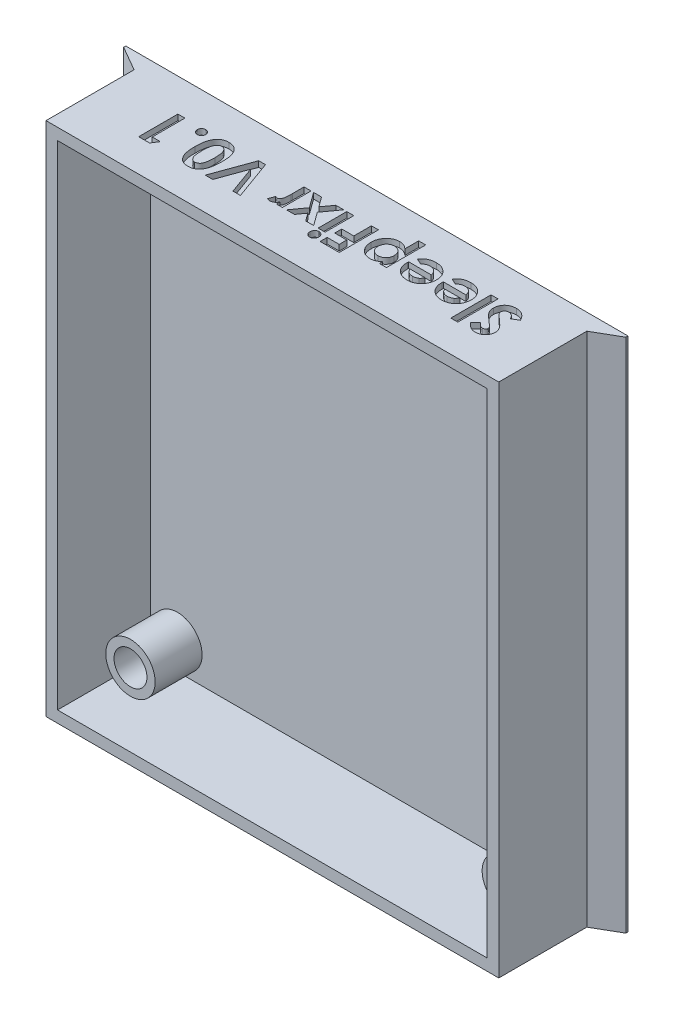
SolidWorks part; units mm, degrees
ref_plane "Front Plane" through (0, 0, 0) normal (0, 0, 1) x (1, 0, 0)
ref_plane "Top Plane" through (0, 0, 0) normal (0, 1, 0) x (1, 0, 0)
ref_plane "Right Plane" through (0, 0, 0) normal (1, 0, 0) x (0, 0, -1)
sketch "Sketch1" plane through (0, 0, 0) normal (0, 0, 1) x (1, 0, 0)
  line L0 (-27.5, 31.35) -> (27.5, -31.35) construction
  line L1 (-27.5, 31.35) -> (27.5, 31.35)
  line L2 (-27.5, 31.35) -> (-27.5, -31.35)
  line L3 (-27.5, -31.35) -> (27.5, -31.35)
  line L4 (27.5, 31.35) -> (27.5, -31.35)
  line L5 (-27.5, -31.35) -> (27.5, 31.35) construction
  point P4 (0, 0)
  dimension "D1" = 55
  dimension "D2" = 62.7
extrude "Boss-Extrude1" add sketch "Sketch1" along normal blind 12.7
shell "Shell1" thickness 1.4 removed face at (0, 0, 12.7)
sketch "Sketch2" plane through (0, 0, 1.4) normal (0, 0, 1) x (1, 0, 0)
  line L0 (24.4065, 26.6523) -> (21.3585, 26.6523) construction
  line L1 (22.8825, 28.1763) -> (22.8825, 25.1283) construction
  circle A0 centre (22.8825, 26.6523) radius 3
  circle A1 centre (22.8825, -26.6878) radius 2
  circle A2 centre (22.8825, 26.6523) radius 2
  circle A3 centre (22.8825, 26.6523) radius 1.524 construction
  circle A4 centre (22.8825, -26.6878) radius 3
  circle A5 centre (-22.8376, -26.6878) radius 3
  circle A6 centre (-22.8376, -26.6878) radius 2
  dimension "D1" = 6
  dimension "D2" = 26.6523
  dimension "D3" = 22.8825
  dimension "D4" = 4
  dimension "D5" = 2
  dimension "D6" = 53.3401
  dimension "D8" = 45.7201
  dimension "D7" = 2
extrude "Boss-Extrude2" add sketch "Sketch2" along normal blind 5.7
sketch "Sketch3" plane through (0, 0, 0) normal (0, 0, -1) x (-1, 0, 0)
  line L0 (27.5, -31.35) -> (-27.5, -31.35) construction
  line L1 (-27.5, 31.35) -> (-30.5, 31.35)
  line L2 (-27.5, 31.35) -> (-27.5, -31.35)
  line L3 (-27.5, -31.35) -> (-30.5, -31.35)
  line L4 (-30.5, 31.35) -> (-30.5, -31.35)
  line L5 (0, 31.35) -> (0, -31.35) construction
  line L6 (-27.5, 31.35) -> (27.5, 31.35) construction
  dimension "D1" = 3
extrude "Boss-Extrude3" add sketch "Sketch3" against normal blind 2
chamfer "Chamfer1" distance 3 angle 30 1 edges at (30.5, 0, 2) first distance on face at (29, 0, 2)
ref_plane "Plane1" through (0, 0, 0) normal (-1, 0, 0) x (0, 0, 1)
mirror "Mirror1" about plane through (0, 0, 0) normal (-1, 0, 0) of "Chamfer1", "Boss-Extrude3"
sketch "Sketch4" plane through (0, 31.35, 0) normal (0, 1, 0) x (1, 0, 0)
  line L0 (-27.5, -4) -> (27.5, -4) construction
  text T0 "<b>SleepFixr V0.1</b>" font "Century Gothic" height in points 18
  point P4 (0, 0)
  dimension "D1" = 4
  dimension "D2" = 55
  dimension "D3" = 27.5
extrude "Cut-Extrude1" cut sketch "Sketch4" against normal blind 0.7
